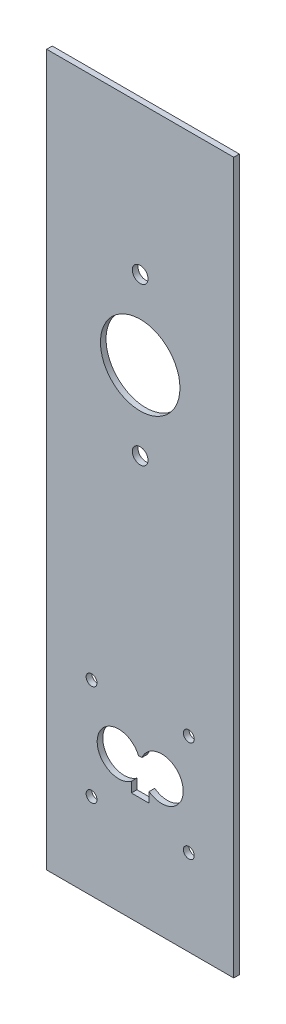
SolidWorks part; units mm, degrees
note: The reader was unsure of these and kept them because the rebuilt part matched: shared geometry of "Sketch1<4>".
ref_plane "Front Plane" through (0, 0, 0) normal (0, 0, 1) x (1, 0, 0)
ref_plane "Top Plane" through (0, 0, 0) normal (0, 1, 0) x (1, 0, 0)
ref_plane "Right Plane" through (0, 0, 0) normal (1, 0, 0) x (0, 0, -1)
sketch "Sketch1" plane through (0, 0, 0) normal (0, 0, 1) x (1, 0, 0)
  line L0 (0, 260) -> (100, 260)
  line L1 (0, 0) -> (100, 0)
  line L2 (0, 0) -> (0, 380)
  line L3 (0, 380) -> (100, 380)
  line L4 (100, 0) -> (100, 380)
  line L6 (18, 106) -> (82, 106)
  line L12 (18, 106) -> (18, 40)
  line L13 (18, 40) -> (82, 40)
  line L25 (82, 106) -> (82, 40)
  line L26 (45.25, 58.3) -> (50, 58.3)
  line L27 (50, 58.3) -> (54.75, 58.3)
  line L29 (45.25, 58.3) -> (45.25, 63.6894)
  line L31 (54.75, 58.3) -> (54.75, 63.6894)
  line L33 (49.083, 77.5) -> (50.917, 77.5)
  circle A8 centre (24, 100) radius 2.9
  circle A9 centre (76, 100) radius 2.9
  circle A10 centre (24, 46) radius 2.9
  circle A11 centre (76, 46) radius 2.9
  arc A14 (49.083, 77.5) -> (45.25, 63.6894) centre (38.5, 73) ccw
  arc A15 (54.75, 63.6894) -> (50.917, 77.5) centre (61.5, 73) ccw
  circle A16 centre (50, 258.75) radius 21.25
  circle A17 centre (50, 300.75) radius 4.2
  circle A18 centre (50, 216.75) radius 4.2
  point P0 (0, 0)
  point P32 (50, 380)
  point P36 (0, 0)
  point P37 (0, 0)
  point P38 (0, 0)
  point P39 (0, 0)
  dimension "D5" = 66
  dimension "D6" = 18
  dimension "D7" = 40
  dimension "D8" = 52
  dimension "D11" = 5.8
  dimension "D12" = 5.8
  dimension "D13" = 5.8
  dimension "D9" = 54
  dimension "D10" = 5.8
  dimension "D14" = 6
  dimension "D15" = 6
  dimension "D16" = 23
  dimension "D17" = 23
  dimension "D21" = 4.75
  dimension "D20" = 33
  dimension "D25" = 20.5
  dimension "D27" = 42.5
  dimension "D28" = 100
  dimension "D29" = 8.4
  dimension "D30" = 8.4
  dimension "D1" = 100
  dimension "D2" = 380
  dimension "D3" = 120
  dimension "D4" = 64
  dimension "D18" = 23
  dimension "D19" = 20.5
  dimension "D22" = 4.75
  dimension "D23" = 32
  dimension "D24" = 14.7
  dimension "D26" = 4.5
  dimension "D31" = 42
  dimension "D32" = 42
extrude "Boss-Extrude1" add sketch "Sketch1" against normal blind 3 contours L4 L3 L2 L1
extrude "Cut-Extrude1" cut sketch "Sketch1<4>" against normal blind 10 contours A8 | A9 | A10 | L31 A15 L33 A14 L29 L26 L27 | A17 | A16 | A18 | A11
sketch "Sketch1<4>" plane through (0, 0, 0) normal (0, 0, 1) x (1, 0, 0) same geometry as "Sketch1"
